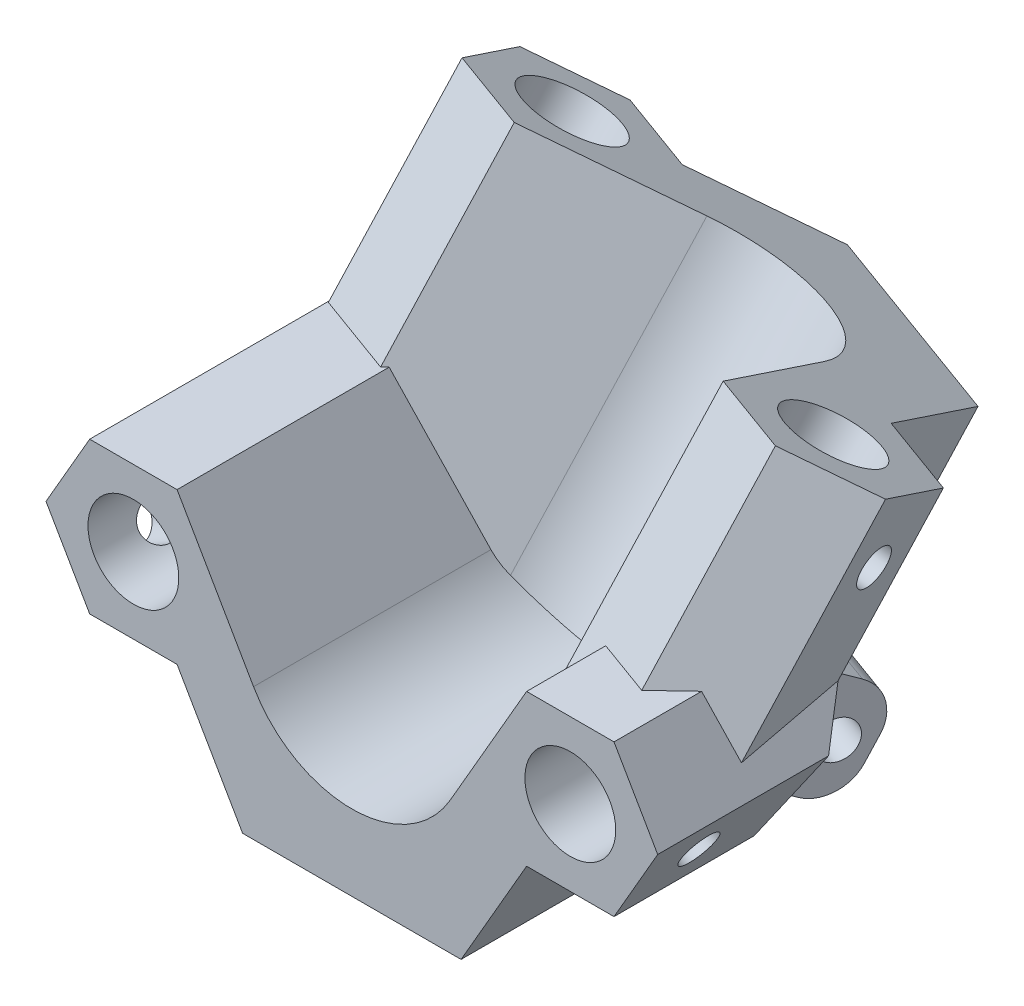
SolidWorks part; units mm, degrees
ref_plane "Front Plane" through (0, 0, 0) normal (0, 0, 1) x (1, 0, 0)
ref_plane "Top Plane" through (0, 0, 0) normal (0, 1, 0) x (1, 0, 0)
ref_plane "Right Plane" through (0, 0, 0) normal (1, 0, 0) x (0, 0, -1)
sketch "Sketch2" plane through (0, 0, 0) normal (0, 1, 0) x (1, 0, 0)
  line L0 (0, 0) -> (0, -10) construction
  line L1 (0, 0) -> (3.4202, 9.3969) construction
  dimension "D1" = 10
  dimension "D2" = 10
  dimension "D3" = 160
ref_plane "Plane1" through (0, 0, 0) normal (0.9397, 0, 0.342) x (0.342, 0, -0.9397)
sketch "Sketch3" plane through (0, 0, 0) normal (0.9397, 0, 0.342) x (0.342, 0, -0.9397)
  line L0 (0, 0) -> (10, 17.3205) construction
  line L1 (10, 17.3205) -> (10, 0) construction
  line L2 (10, 0) -> (0, 0) construction
  dimension "D1" = 30
  dimension "D2" = 10
sketch "Sketch5" plane through (0, 0, 0) normal (0, 0, 1) x (1, 0, 0)
  line L0 (0, 0) -> (10.3923, 0) construction
  line L1 (15.5205, 3.1177) -> (8.6603, 15)
  line L2 (8.6603, 15) -> (-8.6603, 15)
  line L3 (-8.6603, 15) -> (-13.8564, 6)
  line L4 (-13.8564, -6) -> (-8.6603, -15)
  line L5 (-8.6603, -15) -> (8.6603, -15)
  line L6 (8.6603, -15) -> (13.8564, -6)
  line L7 (0, -55) -> (0, 55) construction
  line L8 (24.2487, 0) -> (20.7846, 6)
  line L9 (20.7846, 6) -> (13.8564, 6)
  line L10 (13.8564, 6) -> (7.7942, -4.5)
  line L11 (10.3923, 0) -> (7.7942, 4.5) construction
  line L12 (13.8564, -6) -> (20.7846, -6)
  line L13 (20.7846, -6) -> (24.2487, 0)
  line L14 (-20.7846, -6) -> (-24.2487, 0)
  line L15 (-13.8564, -6) -> (-20.7846, -6)
  line L16 (-7.7942, 4.5) -> (-13.8564, -6) construction
  line L17 (-13.8564, 6) -> (-7.7942, -4.5)
  line L18 (-20.7846, 6) -> (-13.8564, 6)
  line L19 (-24.2487, 0) -> (-20.7846, 6)
  line L20 (-13.8564, 6) -> (-15.5205, 3.1177) construction
  line L21 (-15.5205, 3.1177) -> (-17.3205, 0) construction
  line L22 (-17.3205, 0) -> (-15.5205, -3.1177) construction
  line L23 (-15.5205, -3.1177) -> (-13.8564, -6) construction
  line L24 (-7.7942, -4.5) -> (-10.3923, 0) construction
  line L25 (-10.3923, 0) -> (-7.7942, 4.5) construction
  line L26 (12.1244, -3) -> (13.8564, -6) construction
  line L27 (13.8564, -6) -> (14.3205, -5.1962) construction
  line L28 (15.5205, -3.1177) -> (17.3205, 0) construction
  line L29 (14.3205, -5.1962) -> (15.5205, -3.1177) construction
  line L30 (7.7942, 4.5) -> (12.1244, -3) construction
  line L31 (7.7942, -4.5) -> (10.3923, 0) construction
  line L32 (10.3923, 0) -> (9, 0) construction
  line L33 (9, 0) -> (15, 0) construction
  line L34 (15, 0) -> (17.3205, 0) construction
  line L35 (17.3205, 0) -> (15.5205, 3.1177) construction
  circle A0 centre (0, 0) radius 15 construction
  arc A1 (-7.7942, -4.5) -> (7.7942, -4.5) centre (0, 0) ccw
  circle A2 centre (17.3205, 0) radius 6 construction
  circle A3 centre (17.3205, 0) radius 3.6
  circle A4 centre (-17.3205, 0) radius 3.6
  arc A5 (7.7942, -4.5) -> (-7.7942, -4.5) centre (0, 0) ccw construction
  dimension "D2" = 18
  dimension "D4" = 7.2
  dimension "D1" = 30
  dimension "D3" = 12
extrude "Boss-Extrude2" add sketch "Sketch5" along normal blind 15 contours A4 | L17 A1 L10 L9 L8 L13 L12 L6 L5 L4 L15 L14 L19 L18 | A3
ref_plane "Plane2" through (3.4202, 17.3205, -9.3969) normal (0.171, 0.866, -0.4698) x (0.9853, -0.1503, 0.0815)
sketch "Sketch10" plane through (0, 0, 0) normal (0, 0, -1) x (-1, 0, 0)
  line L0 (-7.7942, -4.5) -> (-13.8564, 6)
  line L1 (-13.8564, 6) -> (-20.7846, 6)
  line L2 (-20.7846, 6) -> (-24.2487, 0)
  line L3 (-24.2487, 0) -> (-20.7846, -6)
  line L4 (-20.7846, -6) -> (-13.8564, -6)
  line L5 (-13.8564, -6) -> (-8.6603, -15)
  line L6 (-8.6603, -15) -> (8.6603, -15)
  line L7 (8.6603, -15) -> (13.8564, -6)
  line L8 (13.8564, -6) -> (20.7846, -6)
  line L9 (20.7846, -6) -> (24.2487, 0)
  line L10 (24.2487, 0) -> (20.7846, 6)
  line L11 (20.7846, 6) -> (13.8564, 6)
  line L12 (20.7846, 6) -> (13.8564, 6) construction
  line L13 (13.8564, 6) -> (7.7942, -4.5)
  arc A0 (-7.7942, -4.5) -> (7.7942, -4.5) centre (0, 0) ccw
  arc A1 (-7.7942, -4.5) -> (7.7942, -4.5) centre (0, 0) ccw construction
  arc A2 (7.7942, -4.5) -> (-7.7942, -4.5) centre (0, 0) ccw construction
sketch "Sketch6" plane through (3.4202, 17.3205, -9.3969) normal (0.171, 0.866, -0.4698) x (0.9853, -0.1503, 0.0815)
  line L0 (-4.5094, -14.3061) -> (4.5094, 14.3061) construction
  line L1 (-3.7502, 16.9096) -> (-11.4117, 9.8881)
  line L2 (-15.7398, 1.6924) -> (-15.0192, -1.5568)
  line L3 (-12.769, -11.7026) -> (-4.5094, -14.3061) construction
  line L4 (11.4117, -9.8881) -> (12.096, -9.2609) construction
  line L5 (15.0192, 1.5568) -> (12.769, 11.7026)
  line L6 (12.769, 11.7026) -> (-3.7502, 16.9096)
  line L7 (2.6035, 8.2596) -> (0, 0) construction
  line L8 (-14.3061, 4.5094) -> (16.5193, -5.207) construction
  line L9 (3.7502, -16.9096) -> (11.4117, -9.8881) construction
  line L10 (23.127, -7.2898) -> (21.6269, -0.526)
  line L11 (21.6269, -0.526) -> (15.0192, 1.5568)
  line L12 (15.0192, 1.5568) -> (12.4654, -0.7837) construction
  line L13 (8.7865, 1.9487) -> (11.4117, -9.8881)
  line L14 (11.4117, -9.8881) -> (18.0194, -11.9709)
  line L15 (18.0194, -11.9709) -> (23.127, -7.2898)
  line L16 (-23.127, 7.2898) -> (-21.6269, 0.526)
  line L17 (-21.6269, 0.526) -> (-15.0192, -1.5568)
  line L18 (-15.0192, -1.5568) -> (-6.0809, 6.635)
  line L19 (-10.6616, 6.5061) -> (-11.4117, 9.8881) construction
  line L20 (-11.4117, 9.8881) -> (-18.0194, 11.9709)
  line L21 (-18.0194, 11.9709) -> (-23.127, 7.2898)
  line L22 (-4.5094, -14.3061) -> (3.7502, -16.9096) construction
  line L23 (-15.0192, -1.5568) -> (-12.769, -11.7026) construction
  line L24 (-6.0809, 6.635) -> (-9.9116, 3.1242) construction
  line L25 (-9.9116, 3.1242) -> (-8.7865, -1.9487) construction
  line L26 (-8.7865, -1.9487) -> (-10.6616, 6.5061) construction
  line L27 (-11.4117, 9.8881) -> (-12.096, 9.2609) construction
  line L28 (-13.8653, 7.6394) -> (-16.5193, 5.207) construction
  line L29 (-12.096, 9.2609) -> (-13.8653, 7.6394) construction
  line L30 (-16.5193, 5.207) -> (-14.3061, 4.5094) construction
  line L31 (-16.5193, 5.207) -> (-15.7398, 1.6924) construction
  line L32 (9.9116, -3.1242) -> (8.7865, 1.9487) construction
  line L33 (6.0809, -6.635) -> (9.9116, -3.1242) construction
  line L34 (12.4654, -0.7837) -> (6.0809, -6.635) construction
  line L35 (16.5193, -5.207) -> (15.7615, -1.79) construction
  line L36 (15.7615, -1.79) -> (15.2202, 0.6507) construction
  line L37 (15.2202, 0.6507) -> (15.0192, 1.5568) construction
  line L38 (13.939, -7.5718) -> (16.5193, -5.207) construction
  line L39 (12.096, -9.2609) -> (13.939, -7.5718) construction
  circle A0 centre (0, 0) radius 15 construction
  arc A1 (8.7865, 1.9487) -> (-6.0809, 6.635) centre (0, 0) ccw
  circle A2 centre (16.5193, -5.207) radius 6 construction
  circle A3 centre (16.5193, -5.207) radius 3.5
  circle A4 centre (-16.5193, 5.207) radius 6 construction
  circle A5 centre (-16.5193, 5.207) radius 3.6
  arc A6 (-2.7056, -8.5837) -> (8.7865, 1.9487) centre (0, 0) ccw construction
  arc A7 (-6.0809, 6.635) -> (-2.7056, -8.5837) centre (0, 0) ccw construction
  dimension "D2" = 18
  dimension "D3" = 7
  dimension "D5" = 7.2
  dimension "D1" = 30
  dimension "D4" = 12
  dimension "D6" = 12
extrude "Boss-Extrude3" add sketch "Sketch6" against normal up to surface (37.3205 mm away) contours L18 A1 L13 L14 L15 L10 L11 L5 L6 L1 L20 L21 L16 L17 | A5 | A3 up to face at (0, -15, 7.5)
sketch "Sketch7" plane through (0, 0, 15) normal (0, 0, 1) x (1, 0, 0)
  circle A0 centre (-17.3205, 0) radius 3.6
  circle A1 centre (-17.3205, 0) radius 3.6 construction
  circle A2 centre (0, 0) radius 9
  arc A3 (-7.7942, -4.5) -> (7.7942, -4.5) centre (0, 0) ccw construction
  circle A4 centre (17.3205, 0) radius 3.6
  arc A5 (17.0513, -3.5899) -> (15.6091, -3.1672) centre (17.3205, 0) ccw construction
extrude "Cut-Extrude1" cut sketch "Sketch7" against normal up to surface (15 mm away) up to face at (-10.5422, -2.7775, 0)
sketch "Sketch8" plane through (0, 0, 0) normal (0, 1, 0) x (1, 0, 0)
  line L0 (-24.2487, -15) -> (24.2487, -15)
  line L1 (24.2487, -15) -> (24.2487, -21.7571)
  line L2 (24.2487, -21.7571) -> (-24.2487, -21.7571)
  line L3 (-24.2487, -21.7571) -> (-24.2487, -15)
extrude "Cut-Extrude2" cut sketch "Sketch8" against normal through all both and the other way through all
sketch "Sketch9" plane through (0, 0, 15) normal (0, 0, 1) x (1, 0, 0)
  line L0 (-8.6603, -15) -> (-13.8564, -6)
  line L1 (-13.8564, -6) -> (-20.7846, -6)
  line L2 (-20.7846, -6) -> (-24.2487, 0)
  line L3 (-24.2487, 0) -> (-25.7483, -15)
  line L4 (-25.7483, -15) -> (-8.6603, -15)
  line L5 (8.6603, -15) -> (13.8564, -6)
  line L6 (13.8564, -6) -> (20.7846, -6)
  line L7 (20.7846, -6) -> (24.2487, 0)
  line L8 (24.2487, 0) -> (19.6596, -15)
  line L9 (19.6596, -15) -> (8.6603, -15)
extrude "Cut-Extrude3" cut sketch "Sketch9" against normal through all both and the other way through all
extrude "Boss-Extrude4" add sketch "Sketch10" along normal up to surface (12.8304 mm away) up to face at (6.3157, -3.7874, -13.8064)
sketch "Sketch11" plane through (3.4202, 17.3205, -9.3969) normal (0.171, 0.866, -0.4698) x (0.9853, -0.1503, 0.0815)
  line L0 (-3.7502, 16.9096) -> (-11.4117, 9.8881)
  line L1 (-11.4117, 9.8881) -> (-18.0194, 11.9709)
  line L2 (-18.0194, 11.9709) -> (-24.4549, 6.0728)
  line L3 (-22.6683, -13.1846) -> (-26.1144, 23.959) construction
  line L4 (-24.4549, 6.0728) -> (-26.1144, 23.959)
  line L5 (-26.1144, 23.959) -> (-3.7502, 16.9096)
  line L6 (12.769, 11.7026) -> (15.0192, 1.5568)
  line L7 (15.0192, 1.5568) -> (24.01, -1.2771)
  line L8 (25.1148, -13.1846) -> (23.1081, 8.4437) construction
  line L9 (24.01, -1.2771) -> (23.1081, 8.4437)
  line L10 (23.1081, 8.4437) -> (12.769, 11.7026)
extrude "Cut-Extrude4" cut sketch "Sketch11" against normal through all both and the other way through all
sketch "Sketch12" plane through (-18.1865, -10.5, 0) normal (-0.866, -0.5, 0) x (0, 0, 1)
  line L0 (15, 8.6603) -> (-7.4822, 8.6603) construction
  line L1 (15, 5.1962) -> (15, 12.1244) construction
  line L2 (-8.0554, 5.1962) -> (-6.909, 12.1244) construction
  circle A0 centre (10, 8.6603) radius 1.5
  dimension "D1" = 3
  dimension "D2" = 5
extrude "Cut-Extrude5" cut sketch "Sketch12" against normal up to surface and the other way through all up to face at (-20.9205, 0, 0)
sketch "Sketch13" plane through (18.1865, -10.5, 0) normal (0.866, -0.5, 0) x (0, 0, -1)
  line L0 (-15, 8.6603) -> (-2.6658, 8.6603) construction
  line L1 (-15, 5.1962) -> (-15, 12.1244) construction
  line L2 (-3.8786, 5.1962) -> (-1.453, 12.1244) construction
  circle A0 centre (-10, 8.6603) radius 1.5
  dimension "D1" = 3
  dimension "D2" = 5
extrude "Cut-Extrude6" cut sketch "Sketch13" against normal up to surface (2.7274 mm away) contours A0 up to face at (17.3205, 0, 0.7511)
sketch "Sketch14" plane through (20.1998, -5.25, -2.3247) normal (0.9619, -0.25, -0.1107) x (-0.1071, 0.0278, -0.9939)
  line L0 (1.8237, 21.7181) -> (-5.4703, 8.1224) construction
  line L1 (-1.2289, 23.3557) -> (4.8762, 20.0804) construction
  line L2 (-1.2869, 8.5925) -> (-9.6536, 7.6523) construction
  circle A0 centre (-0.5401, 17.3121) radius 1.5
  dimension "D1" = 3
  dimension "D2" = 5
extrude "Cut-Extrude7" cut sketch "Sketch14" against normal up to surface (2.5726 mm away) up to face at (19.6962, 18.9896, -0.3966)
sketch "Sketch15" plane through (-13.9797, -5.25, -14.765) normal (-0.6657, -0.25, -0.7031) x (-0.7462, 0.223, 0.6272)
  line L0 (3.8464, 21.4524) -> (9.4928, -2.5305) construction
  line L1 (0.4745, 20.6585) -> (7.2183, 22.2463) construction
  line L2 (9.1192, -2.9545) -> (13.7614, 2.3146) construction
  circle A0 centre (4.9923, 16.5855) radius 1.5
  dimension "D1" = 3
  dimension "D2" = 5
extrude "Cut-Extrude8" cut sketch "Sketch15" against normal up to surface (2.6593 mm away) contours A0 up to face at (-12.8558, 19.0372, -12.1566)
sketch "Sketch16" plane through (4.443, -7.5, -12.207) normal (0.2962, -0.5, -0.8138) x (-0.9551, -0.1551, -0.2524)
  line L0 (-3.5809, 19.6768) -> (1.5506, -8.5203) construction
  line L1 (-12.1012, 18.1262) -> (4.9394, 21.2274) construction
  line L2 (10.0709, -6.9697) -> (-4.4154, -9.606) construction
  line L3 (-0.909, -8.9679) -> (-2.3414, -1.0972)
  line L4 (-2.3414, -1.0972) -> (2.5778, -0.202)
  line L5 (2.5778, -0.202) -> (4.0102, -8.0727)
  line L6 (4.0102, -8.0727) -> (-0.909, -8.9679)
  point P8 (0.1182, -0.6496)
  dimension "D1" = 5
  dimension "D2" = 8
extrude "Boss-Extrude5" add sketch "Sketch16" along normal blind 10
sketch "Sketch17" plane through (2.3492, 0, 0.8551) normal (0.9397, 0, 0.342) x (0.342, 0, -0.9397)
  line L0 (19.3205, -16.5359) -> (10.6603, -11.5359) construction
  line L3 (21.3205, -13.0718) -> (17.3205, -20) construction
  line L4 (12.6603, -8.0718) -> (8.6603, -15) construction
  circle A0 centre (17.1554, -15.2859) radius 1.5
  dimension "D1" = 3
  dimension "D2" = 2.5
extrude "Cut-Extrude9" cut sketch "Sketch17" against normal through all
fillet "Fillet1" radius 3 1 edges at (7.292, -13.0718, -20.0347) type face fillet first side face at (5.8111, -10.5718, -15.9657) second side face at (6.608, -16.5359, -18.1553)
fillet "Fillet2" radius 3 1 edges at (5.924, -20, -16.276) type face fillet first side face at (6.3515, -17.8349, -17.4506) second side face at (4.443, -17.5, -12.207)
